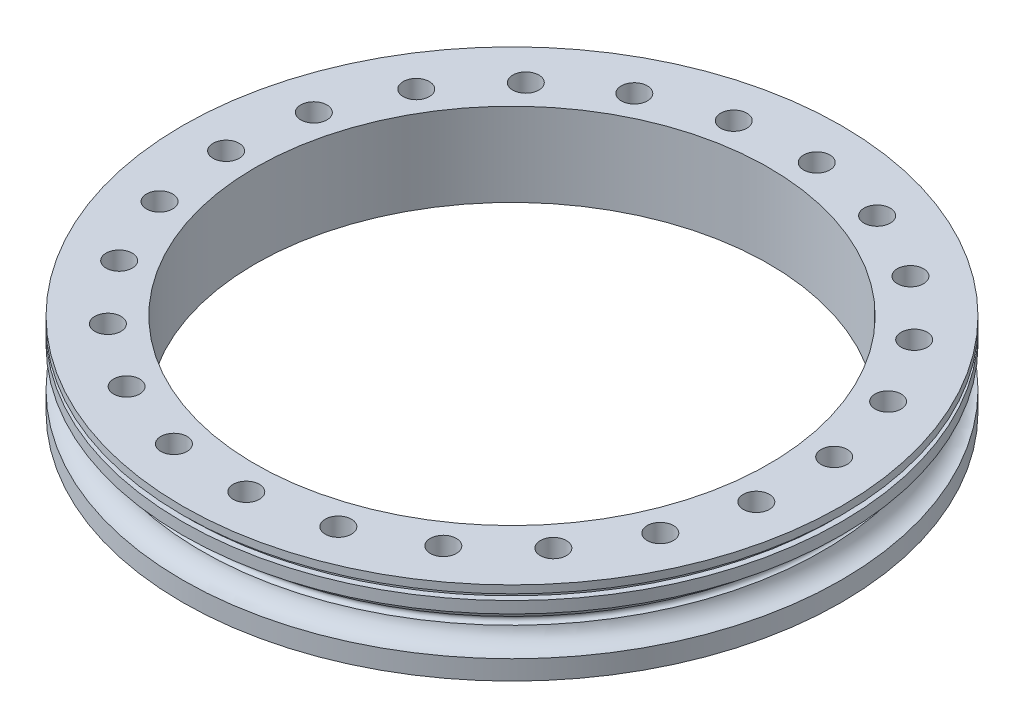
SolidWorks part; units mm, degrees
ref_plane "Plan de face" through (0, 0, 0) normal (0, 0, 1) x (1, 0, 0)
ref_plane "Plan de dessus" through (0, 0, 0) normal (0, 1, 0) x (1, 0, 0)
ref_plane "Plan de droite" through (0, 0, 0) normal (1, 0, 0) x (0, 0, -1)
sketch "Esquisse1" plane through (0, 0, 0) normal (0, 0, 1) x (1, 0, 0)
  line L0 (0, 0) -> (-219.15, 0) construction
  line L1 (-219.15, 0) -> (-219.15, 43) construction
  line L2 (-219.15, 43) -> (0, 43) construction
  line L3 (0, 43) -> (0, 0) construction
  line L4 (-219.15, 0) -> (-172, 0) construction
  line L5 (-172, 0) -> (-172, 10) construction
  line L6 (-172, 10) -> (-172, 30) construction
  line L7 (-172, 43) -> (-172, 42.7532) construction
  line L8 (-172, 43) -> (-219.15, 43) construction
  line L9 (-172, 20) -> (-181.5, 20) construction
  line L10 (-181.5, 20) -> (-183.5, 20) construction
  line L11 (-170, 43) -> (-170, 39)
  line L12 (-170, 39) -> (-167, 39)
  line L13 (-167, 39) -> (-167, 36)
  line L14 (-172, 43) -> (-172, 30) construction
  line L15 (-172, 42.7532) -> (-172, 43) construction
  line L16 (-171, 43) -> (-171, 0) construction
  line L17 (-170, 30) -> (-170, 43) construction
  line L18 (-170, 43) -> (-132.5, 43)
  line L19 (-132.5, 43) -> (-132.5, 0)
  line L20 (-132.5, 0) -> (-170, 0)
  line L21 (-167, 36) -> (-170, 36)
  line L22 (-170, 36) -> (-170, 30)
  line L23 (-170, 0) -> (-170, 10)
  line L24 (-170, 36) -> (-172, 36) construction
  line L25 (-172, 36) -> (-219.15, 36) construction
  line L26 (-219.15, 36) -> (-219.15, -7) construction
  line L27 (-172, 43) -> (-170, 43) construction
  line L28 (-219.15, -7) -> (-172, -7) construction
  line L30 (-172, 0) -> (-172, 3) construction
  line L31 (-172, 3) -> (-175, 3) construction
  line L32 (-175, 3) -> (-175, 0) construction
  line L33 (-175, 0) -> (-172, 0) construction
  line L34 (-172, 0) -> (-172, -7) construction
  arc A0 (-172, 30) -> (-172, 10) centre (-172, 20) ccw construction
  arc A1 (-181.8026, 21.977) -> (-181.8026, 18.023) centre (-181.5, 20) ccw construction
  arc A2 (-181.8026, 18.023) -> (-172, 10) centre (-172, 20) ccw construction
  arc A3 (-172, 30) -> (-181.8026, 21.977) centre (-172, 20) ccw construction
  arc A4 (-160.1974, 21.977) -> (-160.1974, 18.023) centre (-160.5, 20) cw
  arc A5 (-170, 30) -> (-170, 10) centre (-170, 20) cw construction
  arc A6 (-170, 30) -> (-160.1974, 21.977) centre (-170, 20) cw
  arc A7 (-160.1974, 18.023) -> (-170, 10) centre (-170, 20) cw
  dimension "D7" = 10
  dimension "D8" = 9.5
  dimension "D9" = 2
  dimension "D2" = 3
  dimension "D3" = 20
  dimension "D4" = 3
  dimension "D5" = 340
  dimension "D6" = 43
  dimension "D10" = 7
  dimension "D11" = 1
  dimension "D12" = 3
  dimension "D13" = 3
  dimension "D14" = 43
  dimension "D15" = 265
  dimension "D17" = 219.15
revolve "Révolution1" add sketch "Esquisse1" angle 360 about L3
sketch "Esquisse4" plane through (0, 43, 0) normal (0, 1, 0) x (1, 0, 0)
  line L0 (0, 0) -> (-147.5, 0) construction
  circle A0 centre (-147.5, 0) radius 6.75
  point P38 (0, 0)
  dimension "D1" = 13.5
  dimension "D2" = 147.5
extrude "Enlèv. mat.-Extru.2" cut sketch "Esquisse4" against normal through all
ref_axis "Axe2" through (0, 45.15, 0) along (0, -1, 0)
pattern_circular "Répétition circulaire1" count 23 over 360 about axis through (0, 45.15, 0) along (0, -1, 0) of "Enlèv. mat.-Extru.2"
